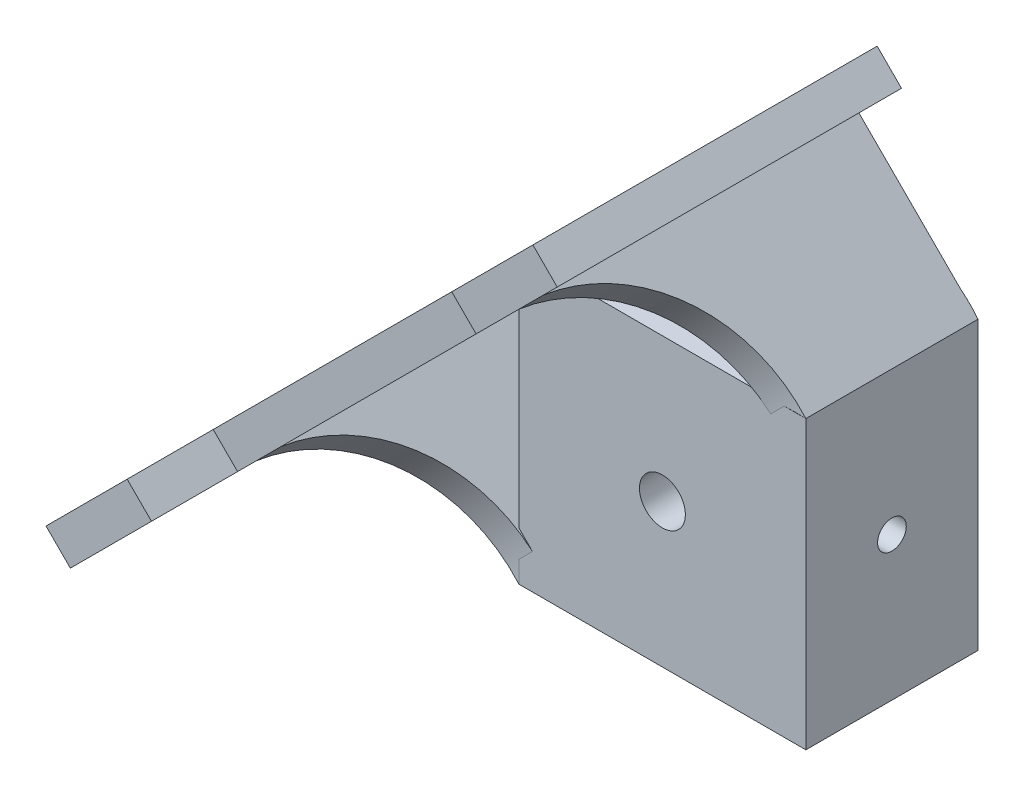
SolidWorks part; units mm, degrees
ref_plane "前视基准面" through (0, 0, 0) normal (0, 0, 1) x (1, 0, 0)
ref_plane "上视基准面" through (0, 0, 0) normal (0, 1, 0) x (1, 0, 0)
ref_plane "右视基准面" through (0, 0, 0) normal (1, 0, 0) x (0, 0, -1)
sketch "草图1" plane through (0, 0, 0) normal (0, 0, 1) x (1, 0, 0)
  line L1 (12.5, 12.5) -> (-12.5, 12.5)
  line L2 (12.5, 12.5) -> (12.5, -12.5)
  line L3 (12.5, -12.5) -> (-12.5, -12.5)
  line L4 (-12.5, 12.5) -> (-12.5, -12.5)
  line L5 (12.5, 12.5) -> (-12.5, -12.5) construction
  line L6 (12.5, -12.5) -> (-12.5, 12.5) construction
  point P0 (0, 0)
extrude "凸台-拉伸1" add sketch "草图1" along normal blind 10
sketch "草图2" plane through (0, 0, 10) normal (0, 0, 1) x (1, 0, 0)
  line L1 (6.25, 6.25) -> (-6.25, 6.25)
  line L2 (6.25, 6.25) -> (6.25, -6.25)
  line L3 (6.25, -6.25) -> (-6.25, -6.25)
  line L4 (-6.25, 6.25) -> (-6.25, -6.25)
  line L5 (6.25, 6.25) -> (-6.25, -6.25) construction
  line L6 (6.25, -6.25) -> (-6.25, 6.25) construction
  point P0 (0, 0)
extrude "切除-拉伸1" cut sketch "草图2" against normal through all
ref_plane "基准面1" through (0, 0, 0) normal (0.7071, -0.7071, 0) x (0, 0, -1)
sketch "草图3" plane through (0, 0, 10) normal (0, 0, 1) x (1, 0, 0)
  line L4 (-12.5, 12.5) -> (-12.5, -12.5)
  line L5 (-12.5, -12.5) -> (12.5, -12.5)
  line L6 (12.5, -12.5) -> (12.5, 12.5)
  line L7 (12.5, 12.5) -> (-12.5, 12.5)
  line L8 (-12.5, 12.5) -> (-12.5, -12.5)
  line L9 (-12.5, -12.5) -> (12.5, -12.5)
  line L10 (12.5, -12.5) -> (12.5, 12.5)
  line L11 (12.5, 12.5) -> (-12.5, 12.5)
  dimension "D1" = 0
extrude "凸台-拉伸2" add sketch "草图3" along normal blind 5
sketch "草图4" plane through (0, 0, 15) normal (0, 0, 1) x (1, 0, 0)
  line L0 (0, 12.5) -> (0, -12.5) construction
  line L1 (12.5, 12.5) -> (-12.5, 12.5) construction
  line L2 (-12.5, -12.5) -> (12.5, -12.5) construction
  line L3 (-12.5, 0) -> (12.5, 0) construction
  line L4 (-12.5, 12.5) -> (-12.5, -12.5) construction
  line L5 (12.5, -12.5) -> (12.5, 12.5) construction
  circle A0 centre (0, 0) radius 2
  dimension "D1" = 4
extrude "切除-拉伸2" cut sketch "草图4" against normal through all
ref_plane "基准面2" through (-12.5, 12.5, 0) normal (0.7071, -0.7071, 0) x (0, 0, -1)
sketch "草图5" plane through (-12.5, 12.5, 0) normal (0.7071, -0.7071, 0) x (0, 0, -1)
  line L1 (-12.5, -20) -> (-27.5, 20) construction
  line L2 (-12.5, -20) -> (-27.5, -20)
  line L3 (-12.5, -20) -> (-12.5, 20)
  line L4 (-12.5, 20) -> (-27.5, 20)
  line L5 (-27.5, -20) -> (-27.5, 20)
  line L6 (-27.5, -20) -> (-12.5, 20) construction
  line L7 (0, 0) -> (-51.2847, 0) construction
  point P7 (-20, 0)
extrude "凸台-拉伸3" add sketch "草图5" along normal blind 3
ref_plane "基准面3" through (-12.5, -12.5, 0) normal (-0.7071, -0.7071, 0) x (0, 0, -1)
ref_plane "基准面4" through (0, 0, 0) normal (-0.7071, -0.7071, 0) x (0, 0, -1)
sketch "草图9" plane through (-10.3787, 10.3787, 0) normal (0.7071, -0.7071, 0) x (0, 0, -1)
  line L0 (-20, 20) -> (-20, 36.2031) construction
  line L1 (-12.5, 20) -> (-27.5, 20) construction
  line L3 (-5, 30) -> (-35, 30)
  line L4 (-5, 30) -> (-5, 20)
  line L5 (-5, 20) -> (-35, 20)
  line L6 (-35, 30) -> (-35, 20)
  line L7 (-5, 30) -> (-35, 20) construction
  line L8 (-5, 20) -> (-35, 30) construction
  point P4 (-20, 25)
extrude "凸台-拉伸7" add sketch "草图9" against normal up to surface (3 mm away) up to face at (-12.5, 12.5, 18.5)
sketch "草图11" plane through (-12.5, 12.5, 0) normal (-0.7071, 0.7071, 0) x (0, 0, 1)
  circle A2 centre (11, 24) radius 1.5
  circle A3 centre (29, 24) radius 1.5
extrude "切除-拉伸3" cut sketch "草图11" against normal through all
sketch "草图12" plane through (0, 0, 12.5) normal (0, 0, -1) x (-1, 0, 0)
  line L0 (-12.5, 12.5) -> (12.5, 12.5) construction
  line L1 (-12.5, 12.5) -> (12.5, 12.5) construction
  line L2 (12.5, 12.5) -> (12.5, -12.5) construction
  line L3 (12.5, 12.5) -> (12.5, -12.5) construction
  line L5 (8.2574, 12.5) -> (12.5, 8.2574)
  line L7 (8.2574, 12.5) -> (10.3787, 14.6213)
  line L8 (12.5, 12.5) -> (-1.6421, 26.6421) construction
  line L9 (12.5, 8.2574) -> (14.6213, 10.3787)
  line L10 (26.6421, -1.6421) -> (12.5, 12.5) construction
  line L11 (14.6213, 10.3787) -> (10.3787, 14.6213)
extrude "凸台-拉伸8" add sketch "草图12" along normal up to surface (12.5 mm away) up to face at (0, 0, 0)
ref_plane "基准面5" through (12.5, 12.5, 0) normal (-0.7071, -0.7071, 0) x (0, 0, -1)
sketch "草图13" plane through (12.5, 12.5, 0) normal (-0.7071, -0.7071, 0) x (0, 0, -1)
  line L0 (-27.5, -14.6777) -> (-27.5, -17.6777) construction
  line L1 (-27.5, -14.6777) -> (-27.5, -17.6777) construction
  line L2 (-12.5, -14.6777) -> (-12.5, -17.6777) construction
  line L3 (-12.5, -14.6777) -> (-12.5, -17.6777) construction
  line L4 (-27.5, -14.6777) -> (-12.5, -14.6777)
  line L5 (0, 0) -> (-15, 0)
  arc A0 (0, 0) -> (-12.5, -14.6777) centre (-13.5888, -1.0888) cw
  arc A1 (-15, 0) -> (-27.5, -14.6777) centre (-29.0854, -0.6659) cw
extrude "凸台-拉伸9" add sketch "草图13" along normal blind 3
sketch "草图15" plane through (12.5, 0, 0) normal (1, 0, 0) x (0, 0, -1)
  line L0 (-15, 0) -> (0, 0) construction
  line L1 (-15, -12.5) -> (-15, 12.5) construction
  line L2 (0, -12.5) -> (0, 12.5) construction
  line L3 (-7.5, -12.5) -> (-7.5, 12.5) construction
  line L4 (-15, -12.5) -> (0, -12.5) construction
  line L5 (-15, 12.5) -> (0, 12.5) construction
  circle A0 centre (-7.5, 0) radius 1.25
extrude "切除-拉伸4" cut sketch "草图15" against normal blind 10
sketch "草图16" plane through (12.5, 12.5, 0) normal (0.7071, 0.7071, 0) x (0, 0, -1)
  line L0 (-12.5, 14.6777) -> (-12.5, 17.6777)
  line L2 (0, 0) -> (0, 17.6777)
  line L3 (0, 17.6777) -> (-12.5, 17.6777) construction
  line L4 (0, 17.6777) -> (-12.5, 17.6777)
  arc A0 (0, 0) -> (-12.5, 14.6777) centre (-13.5888, 1.0888) ccw construction
  arc A1 (0, 0) -> (-12.5, 14.6777) centre (-13.5888, 1.0888) ccw
  arc M5 (0, 0) -> (-12.5, 14.6777) centre (-13.5888, 1.0888) ccw
extrude "凸台-拉伸10" add sketch "草图16" against normal up to surface (3 mm away) contours L2 L4 L0 M5 region at (2.6764, 22.3236, 4.596) up to face at (4.557, 16.2004, 13.1171)
mirror "镜向3" about plane through (0, 0, 0) normal (-0.7071, -0.7071, 0) of "凸台-拉伸10", "凸台-拉伸9", "凸台-拉伸7", "切除-拉伸3", "切除-拉伸4"
